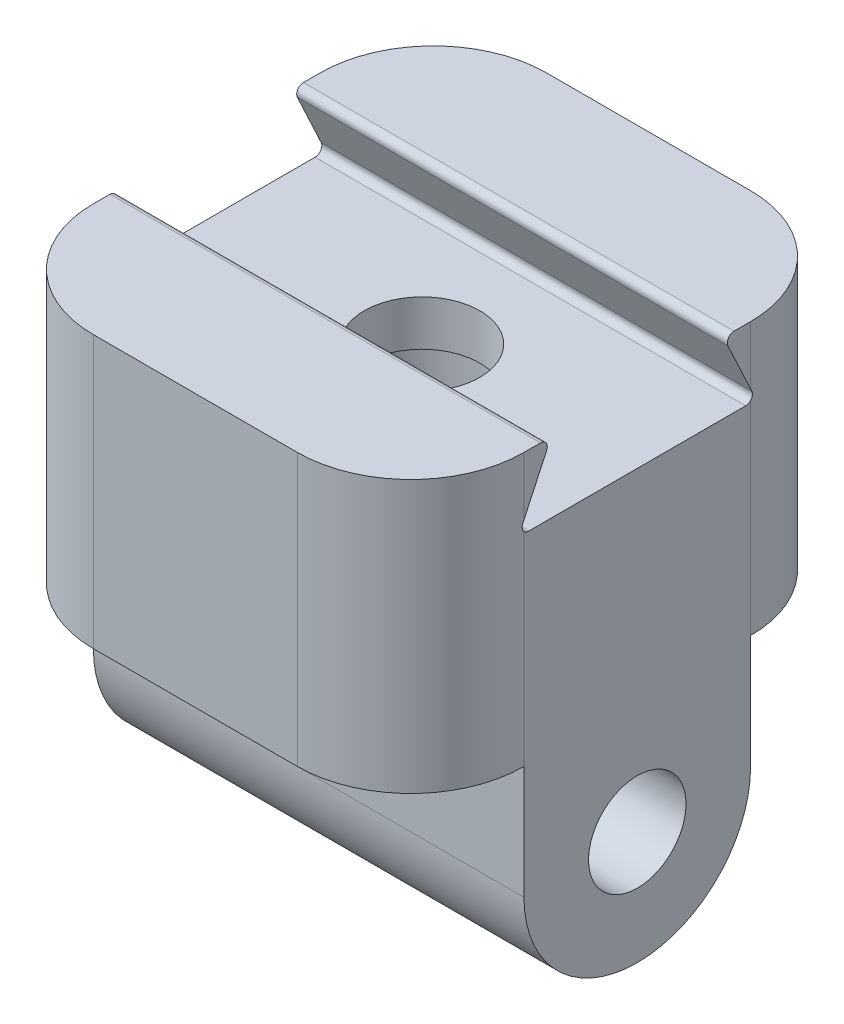
SolidWorks part; units mm, degrees
ref_plane "Front Plane" through (0, 0, 0) normal (0, 0, 1) x (1, 0, 0)
ref_plane "Top Plane" through (0, 0, 0) normal (0, 1, 0) x (1, 0, 0)
ref_plane "Right Plane" through (0, 0, 0) normal (1, 0, 0) x (0, 0, -1)
sketch "Sketch2" plane through (0, 0, 0) normal (0, 1, 0) x (1, 0, 0)
  line L1 (9.5, 10) -> (-9.5, 10)
  line L2 (9.5, 10) -> (9.5, -10)
  line L3 (9.5, -10) -> (-9.5, -10)
  line L4 (-9.5, 10) -> (-9.5, -10)
  line L5 (9.5, 10) -> (-9.5, -10) construction
  line L6 (9.5, -10) -> (-9.5, 10) construction
  point P0 (0, 0)
  dimension "D1" = 19
  dimension "D2" = 20
extrude "Boss-Extrude1" add sketch "Sketch2" along normal blind 12
sketch "Sketch3" plane through (9.5, 0, 0) normal (1, 0, 0) x (0, 0, -1)
  line L0 (-3.8, 12) -> (3.8, 12)
  line L1 (-10, 12) -> (10, 12) construction
  line L2 (3.8, 12) -> (5.25, 8.8905)
  line L3 (5.25, 8.8905) -> (-5.25, 8.8905)
  line L4 (0, 12) -> (0, 0) construction
  line L5 (-3.8, 12) -> (-5.25, 8.8905)
  point P11 (0, 8.8905)
  dimension "D1" = 3.8
  dimension "D2" = 5.25
  dimension "D3" = 65
extrude "Cut-Extrude1" cut sketch "Sketch3" against normal through all
fillet "Fillet1" radius 5 4 edges at (-9.5, 6, 10) (-9.5, 6, -10) (9.5, 6, -10) (9.5, 6, 10)
fillet "Fillet2" radius 0.3 4 edges at (0, 12, 3.8) (0, 12, -3.8) (0, 8.8905, -5.25) (0, 8.8905, 5.25)
sketch "Sketch4" plane through (0, 8.8905, 0) normal (0, 1, 0) x (1, 0, 0)
  circle A0 centre (0, 0) radius 2.55
  dimension "D1" = 5.1
extrude "Cut-Extrude2" cut sketch "Sketch4" against normal blind 2
sketch "Sketch5" plane through (0, 6.8905, 0) normal (0, 1, 0) x (1, 0, 0)
  circle A0 centre (0, 0) radius 2.9
  dimension "D1" = 5.8
extrude "Cut-Extrude3" cut sketch "Sketch5" against normal blind 6
sketch "Sketch6" plane through (0, 0, 0) normal (0, -1, 0) x (1, 0, 0)
  line L0 (-9.5, -5) -> (-9.5, 5) construction
  line L1 (9.5, 5) -> (-9.5, 5)
  line L2 (9.5, 5) -> (9.5, -5)
  line L3 (9.5, -5) -> (-9.5, -5)
  line L4 (-9.5, 5) -> (-9.5, -5)
  line L5 (9.5, 5) -> (-9.5, -5) construction
  line L6 (9.5, -5) -> (-9.5, 5) construction
  point P0 (0, 0)
  dimension "D2" = 10
extrude "Boss-Extrude2" add sketch "Sketch6" along normal blind 10
sketch "Sketch7" plane through (9.5, 0, 0) normal (1, 0, 0) x (0, 0, -1)
  line L0 (5, -10) -> (5, 0) construction
  circle A0 centre (0, -5) radius 2.15
  point P5 (5, -5)
  dimension "D1" = 4.3
extrude "Cut-Extrude4" cut sketch "Sketch7" against normal through all
fillet "Fillet3" radius 5 2 edges at (0, -10, -5) (0, -10, 5)
